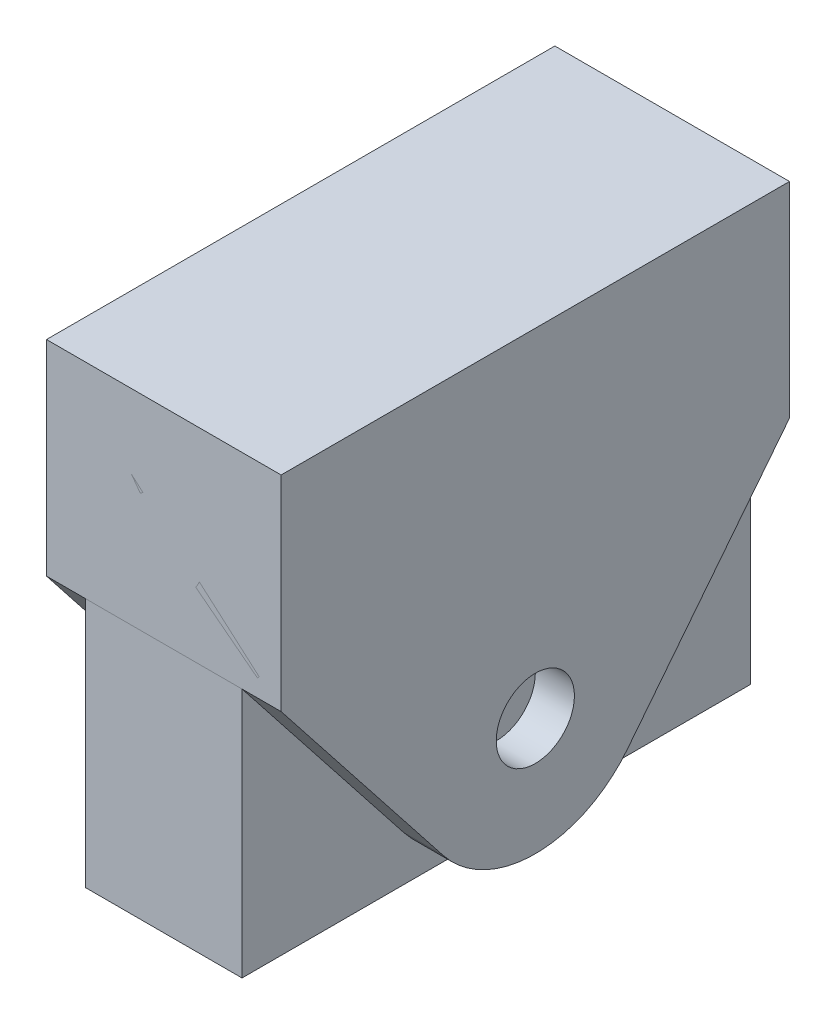
SolidWorks part; units mm, degrees
ref_plane "Front Plane" through (0, 0, 0) normal (0, 0, 1) x (1, 0, 0)
ref_plane "Top Plane" through (0, 0, 0) normal (0, 1, 0) x (1, 0, 0)
ref_plane "Right Plane" through (0, 0, 0) normal (1, 0, 0) x (0, 0, -1)
sketch "Sketch1" plane through (0, 0, 0) normal (0, 0, 1) x (1, 0, 0)
  line L0 (0, 0) -> (0, 5.0831)
  line L1 (3.175, 5.0831) -> (3.175, 0)
  line L2 (3.175, 0) -> (0, 0)
  arc A0 (0, 5.0831) -> (3.175, 5.0831) centre (1.5875, 6.858) cw
  circle A1 centre (1.5875, 6.858) radius 0.7938
  dimension "D2" = 2.3813
  dimension "D4" = 1.5875
  dimension "D1" = 6.858
  dimension "D3" = 3.175
sketch "Sketch2" plane through (0, 0, 0) normal (1, 0, 0) x (0, 0, -1)
  line L0 (-1.8701, 0.9071) -> (-5.1594, 5.08)
  line L1 (-5.1594, 5.08) -> (-5.1594, 9.2392)
  line L2 (-5.1594, 9.2392) -> (5.1594, 9.2392)
  line L3 (5.1594, 9.2392) -> (5.1594, 5.08)
  line L4 (5.1594, 5.08) -> (1.8701, 0.9071)
  arc A0 (1.8701, 0.9071) -> (-1.8701, 0.9071) centre (0, 2.3813) cw
  circle A1 centre (0, 2.3813) radius 0.7938
  point P3 (0, 0)
  point P11 (-5.1594, 6.858)
  dimension "D1" = 2.3813
  dimension "D6" = 1.5875
  dimension "D2" = 5.1594
  dimension "D3" = 5.08
  dimension "D4" = 2.3813
  dimension "D5" = 6.858
extrude "Boss-Extrude1" add sketch "Sketch1" along normal blind 5.1594 and the other way blind 5.1594
extrude "Boss-Extrude2" add sketch "Sketch2" along normal blind 3.9688 and the other way blind 0.7937 separate body
equation "\"D4@Sketch2\"= \"D2@Sketch1\""
equation "\"D5@Sketch2\"= \"D1@Sketch1\""
equation "\"D1@Boss-Extrude1\"= \"D2@Sketch2\""
equation "\"D2@Boss-Extrude1\" = \"D1@Boss-Extrude1\""
equation "\"D1@Boss-Extrude2\"= \"D2@Sketch1\" + ( \"D3@Sketch1\" / 2 )"
equation "\"D2@Boss-Extrude2\"= \"D2@Sketch1\" - ( \"D3@Sketch1\" / 2 )"
